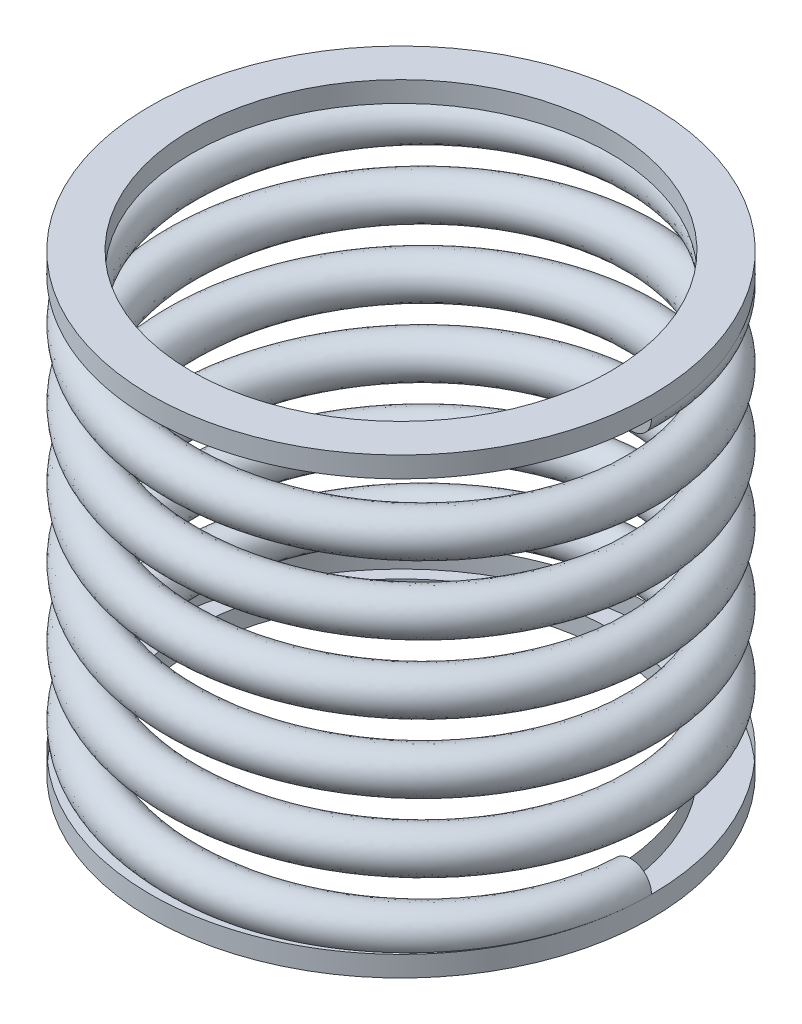
SolidWorks part; units mm, degrees
ref_plane "前视" through (0, 0, 0) normal (0, 0, 1) x (1, 0, 0)
ref_plane "上视" through (0, 0, 0) normal (0, 1, 0) x (1, 0, 0)
ref_plane "右视" through (0, 0, 0) normal (1, 0, 0) x (0, 0, -1)
sketch "草图1" plane through (0, 0, 0) normal (0, 1, 0) x (1, 0, 0)
  circle A0 centre (0, 0) radius 16.75
  dimension "D1" = 33.5
curve "螺旋线/涡状线1" pitch 5 height 30 radius 16.75 left hand yes centre (0, 0, 0) axis (0, 1, 0) start towards (1, 0, 0)
sketch "草图3" plane through (0, 0, 0) normal (0, 0, 1) x (1, 0, 0)
  circle A0 centre (16.75, 0) radius 1.5
  spline S0 degree 3 poles (16.75, 0) (16.75, 0.0921) (16.0628, 0.278) (13.0945, 0.5555) (8.5468, 0.8333) (2.9683, 1.1111) (-2.9683, 1.3889) (-8.5468, 1.6667) (-13.0945, 1.9444) (-16.0628, 2.2222) (-17.0936, 2.5) (-16.0628, 2.7778) (-13.0945, 3.0556) (-8.5468, 3.3333) (-2.9683, 3.6111) (2.9683, 3.8889) (8.5468, 4.1667) (13.0945, 4.4444) (16.0628, 4.7222) (17.0936, 5) (16.0628, 5.2778) (13.0945, 5.5556) (8.5468, 5.8333) (2.9683, 6.1111) (-2.9683, 6.3889) (-8.5468, 6.6667) (-13.0945, 6.9444) (-16.0628, 7.2222) (-17.0936, 7.5) (-16.0628, 7.7778) (-13.0945, 8.0556) (-8.5468, 8.3333) (-2.9683, 8.6111) (2.9683, 8.8889) (8.5468, 9.1667) (13.0945, 9.4444) (16.0628, 9.7222) (17.0936, 10) (16.0628, 10.2778) (13.0945, 10.5556) (8.5468, 10.8333) (2.9683, 11.1111) (-2.9683, 11.3889) (-8.5468, 11.6667) (-13.0945, 11.9444) (-16.0628, 12.2222) (-17.0936, 12.5) (-16.0628, 12.7778) (-13.0945, 13.0556) (-8.5468, 13.3333) (-2.9683, 13.6111) (2.9683, 13.8889) (8.5468, 14.1667) (13.0945, 14.4444) (16.0628, 14.7222) (17.0936, 15) (16.0628, 15.2778) (13.0945, 15.5556) (8.5468, 15.8333) (2.9683, 16.1111) (-2.9683, 16.3889) (-8.5468, 16.6667) (-13.0945, 16.9444) (-16.0628, 17.2222) (-17.0936, 17.5) (-16.0628, 17.7778) (-13.0945, 18.0556) (-8.5468, 18.3333) (-2.9683, 18.6111) (2.9683, 18.8889) (8.5468, 19.1667) (13.0945, 19.4444) (16.0628, 19.7222) (17.0936, 20) (16.0628, 20.2778) (13.0945, 20.5556) (8.5468, 20.8333) (2.9683, 21.1111) (-2.9683, 21.3889) (-8.5468, 21.6667) (-13.0945, 21.9444) (-16.0628, 22.2222) (-17.0936, 22.5) (-16.0628, 22.7778) (-13.0945, 23.0556) (-8.5468, 23.3333) (-2.9683, 23.6111) (2.9683, 23.8889) (8.5468, 24.1667) (13.0945, 24.4444) (16.0628, 24.7222) (17.0936, 25) (16.0628, 25.2778) (13.0945, 25.5556) (8.5468, 25.8333) (2.9683, 26.1111) (-2.9683, 26.3889) (-8.5468, 26.6667) (-13.0945, 26.9444) (-16.0628, 27.2222) (-17.0936, 27.5) (-16.0628, 27.7778) (-13.0945, 28.0556) (-8.5468, 28.3333) (-2.9683, 28.6111) (2.9683, 28.8889) (8.5468, 29.1667) (13.0945, 29.4445) (16.0628, 29.722) (16.75, 29.9079) (16.75, 30) knots 0 0 0 0 0.009259 0.018519 0.027778 0.037037 0.046296 0.055556 0.064815 0.074074 0.083333 0.092593 0.101852 0.111111 0.12037 0.12963 0.138889 0.148148 0.157407 0.166667 0.175926 0.185185 0.194444 0.203704 0.212963 0.222222 0.231481 0.240741 0.25 0.259259 0.268519 0.277778 0.287037 0.296296 0.305556 0.314815 0.324074 0.333333 0.342593 0.351852 0.361111 0.37037 0.37963 0.388889 0.398148 0.407407 0.416667 0.425926 0.435185 0.444444 0.453704 0.462963 0.472222 0.481481 0.490741 0.5 0.509259 0.518519 0.527778 0.537037 0.546296 0.555556 0.564815 0.574074 0.583333 0.592593 0.601852 0.611111 0.62037 0.62963 0.638889 0.648148 0.657407 0.666667 0.675926 0.685185 0.694444 0.703704 0.712963 0.722222 0.731481 0.740741 0.75 0.759259 0.768519 0.777778 0.787037 0.796296 0.805556 0.814815 0.824074 0.833333 0.842593 0.851852 0.861111 0.87037 0.87963 0.888889 0.898148 0.907407 0.916667 0.925926 0.935185 0.944444 0.953704 0.962963 0.972222 0.981481 0.990741 1 1 1 1 construction
  dimension "D1" = 3
sweep "扫描2" add profiles "草图3" path "螺旋线/涡状线1"
sketch "草图4" plane through (0, 0, 0) normal (0, 1, 0) x (1, 0, 0)
  circle A0 centre (0, 0) radius 16.75 construction
  circle A1 centre (0, 0) radius 18.25
  circle A2 centre (0, 0) radius 15.25
  dimension "D1" = 33.5
  dimension "D2" = 1.5
  dimension "D3" = 1.5
extrude "凸台-拉伸1" add sketch "草图4" against normal blind 1.5
ref_plane "基准面2" through (0, 30, 0) normal (0, 1, 0) x (1, 0, 0)
sketch "草图5" plane through (0, 30, 0) normal (0, 1, 0) x (1, 0, 0)
  circle A0 centre (0, 0) radius 16.75 construction
  circle A1 centre (0, 0) radius 18.25
  circle A2 centre (0, 0) radius 15.25
  dimension "D1" = 33.5
  dimension "D2" = 1.5
  dimension "D3" = 1.5
extrude "凸台-拉伸2" add sketch "草图5" along normal blind 1.5
